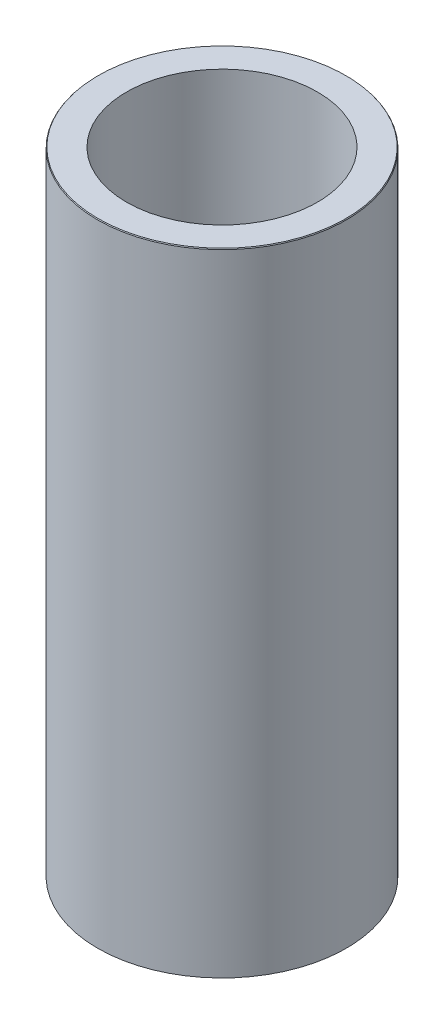
SolidWorks part; units mm, degrees
ref_plane "Front Plane" through (0, 0, 0) normal (0, 0, 1) x (1, 0, 0)
ref_plane "Top Plane" through (0, 0, 0) normal (0, 1, 0) x (1, 0, 0)
ref_plane "Right Plane" through (0, 0, 0) normal (1, 0, 0) x (0, 0, -1)
sketch "Sketch1" plane through (0, 0, 0) normal (0, 1, 0) x (1, 0, 0)
  circle A0 centre (0, 0) radius 52.5
  dimension "SHAFT_OD" = 105
extrude "Boss-Extrude1" add sketch "Sketch1" along normal blind 266.7588
sketch "Sketch2" plane through (0, 0, 0) normal (0, 1, 0) x (1, 0, 0)
  circle A0 centre (0, 0) radius 40.2956
  dimension "BORE_D" = 80.5911
extrude "Cut-Extrude1" cut sketch "Sketch2" along normal through all
chamfer "Chamfer1" distance 0.3712 angle 31.585 2 edges at (0, 266.7588, 52.5) (0, 0, 52.5) first distance on face at (0, 266.7588, 52.5) first distance on face at (0, 0, 40.2956)
